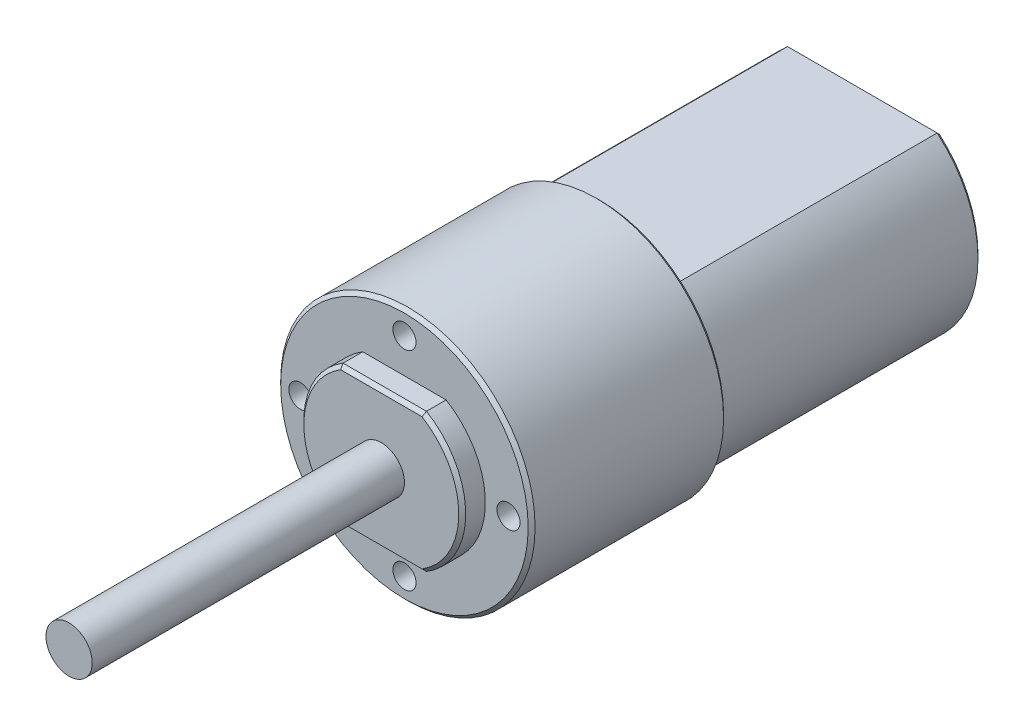
SolidWorks part; units mm, degrees
ref_plane "Front Plane" through (0, 0, 0) normal (0, 0, 1) x (1, 0, 0)
ref_plane "Top Plane" through (0, 0, 0) normal (0, 1, 0) x (1, 0, 0)
ref_plane "Right Plane" through (0, 0, 0) normal (1, 0, 0) x (0, 0, -1)
sketch "Sketch1" plane through (0, 0, 0) normal (0, 1, 0) x (1, 0, 0)
  line L0 (0, 0.2875) -> (0, 37.1846) construction
  line L1 (-2, -29) -> (-2, -2)
  line L2 (-2, -29) -> (0, -29)
  line L3 (-2, -2) -> (-7, -2)
  line L4 (-7, -2) -> (-7, 0)
  line L5 (-7, 0) -> (-11, 0)
  line L6 (-11, 0) -> (-11, 16.9)
  line L7 (-11, 16.9) -> (-10, 16.9)
  line L8 (-10, 16.9) -> (-10, 39.9)
  line L9 (-10, 39.9) -> (0, 39.9)
  line L10 (0, 39.9) -> (0, -29)
  dimension "D1" = 4
  dimension "D2" = 27
  dimension "D3" = 2
  dimension "D4" = 22
  dimension "D5" = 14
  dimension "D6" = 16.9
  dimension "D7" = 41.9
  dimension "D8" = 20
revolve "Revolve1" add sketch "Sketch1" angle 360 about L0
sketch "Sketch2" plane through (0, 0, -39.9) normal (0, 0, -1) x (-1, 0, 0)
  line L0 (-6.4699, 7.625) -> (6.4699, 7.625)
  line L1 (-6.4699, -7.625) -> (6.4699, -7.625)
  line L2 (0, 0) -> (16.0467, 0) construction
  circle A0 centre (0, 0) radius 10 construction
  circle A2 centre (0, 0) radius 10
  circle A3 centre (0, 0) radius 10
  circle M5 centre (0, 0) radius 10
  dimension "D1" = 15.25
  dimension "D2" = 0
extrude "Cut-Extrude1" cut sketch "Sketch2" against normal up to surface (23 mm away) contours L0 M5 | L1 M5 region at (0, 8.5854, -39.9) region at (0, -8.5854, -39.9) up to face at (11, 0, -16.9)
sketch "Sketch3" plane through (0, 0, 0) normal (0, 0, 1) x (1, 0, 0)
  circle A0 centre (0, 9) radius 1
  circle A1 centre (0, 0) radius 9 construction
  circle A2 centre (9, 0) radius 1
  circle A3 centre (0, -9) radius 1
  circle A4 centre (-9, 0) radius 1
  point P15 (0, 0)
  dimension "D1" = 18
  dimension "D2" = 2
  dimension "D3" = 4
extrude "Cut-Extrude2" cut sketch "Sketch3" against normal blind 10
sketch "Sketch4" plane through (0, 0, 2) normal (0, 0, 1) x (1, 0, 0)
  line L0 (-3.6056, 6) -> (3.6056, 6)
  line L1 (-3.6056, -6) -> (3.6056, -6)
  line L2 (0, 0) -> (4.6997, 0) construction
  circle A0 centre (0, 0) radius 7 construction
  circle A1 centre (0, 0) radius 7 construction
  circle A3 centre (0, 0) radius 7
  circle A4 centre (0, 0) radius 7
  circle M6 centre (0, 0) radius 7
  dimension "D1" = 12
  dimension "D2" = 0
extrude "Cut-Extrude3" cut sketch "Sketch4" against normal up to surface (2 mm away) contours L0 M6 | L1 M6 region at (0, 6.4026, 2) region at (0, -6.4026, 2) up to face at (1, 9, 0)
chamfer "Chamfer1" distance 0.3 angle 45 10 edges at (0, -7.625, -39.9) (10, 0, -39.9) (0, 7.625, -39.9) (-10, 0, -39.9) (11, 0, 0) (11, 0, -16.9) (-7, 0, 2) (0, -6, 2) (7, 0, 2) (0, 6, 2)
